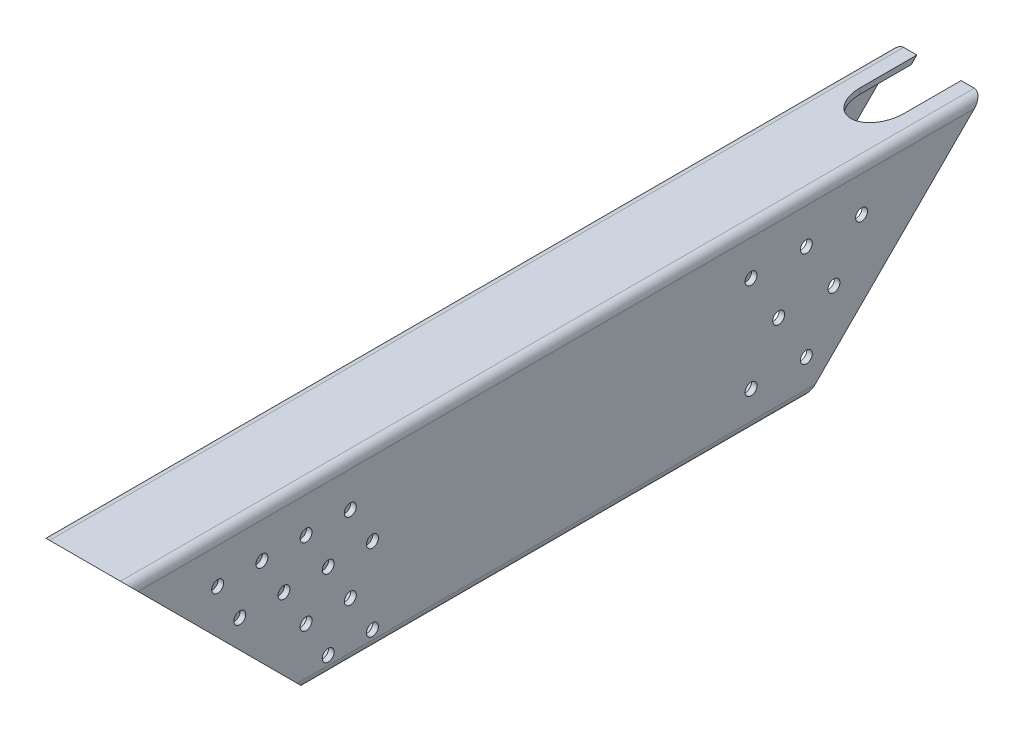
SolidWorks part; units mm, degrees
material "6061-T6 (SS)"
ref_plane "Front" through (0, 0, 0) normal (0, 0, 1) x (1, 0, 0)
ref_plane "Top" through (0, 0, 0) normal (0, 1, 0) x (1, 0, 0)
ref_plane "Right" through (0, 0, 0) normal (1, 0, 0) x (0, 0, -1)
sketch "Sketch3" plane through (0, 0, 0) normal (1, 0, 0) x (0, 0, -1)
  line L0 (-50.8, -25.4) -> (-194.4841, -25.4)
  line L1 (-194.4841, -25.4) -> (-245.2841, 25.4)
  line L2 (-245.2841, 25.4) -> (0, 25.4)
  line L3 (0, 25.4) -> (-50.8, -25.4)
  point P8 (-25.4, 0)
  dimension "D1" = 50.8
  dimension "D2" = 101.6
  dimension "D3" = 45
sketch "Sketch1" plane through (0, 0, 0) normal (0, 0, 1) x (1, 0, 0)
  line L1 (-10.16, -25.4) -> (10.16, -25.4)
  line L2 (-12.7, -22.86) -> (-12.7, 22.86)
  line L3 (-10.16, 25.4) -> (10.16, 25.4)
  line L4 (12.7, -22.86) -> (12.7, 22.86)
  line L5 (-12.7, -25.4) -> (12.7, 25.4) construction
  line L6 (-12.7, 25.4) -> (12.7, -25.4) construction
  arc A0 (-10.16, -25.4) -> (-12.7, -22.86) centre (-10.16, -22.86) cw
  arc A1 (10.16, -25.4) -> (12.7, -22.86) centre (10.16, -22.86) ccw
  arc A2 (10.16, 25.4) -> (12.7, 22.86) centre (10.16, 22.86) cw
  arc A3 (-12.7, 22.86) -> (-10.16, 25.4) centre (-10.16, 22.86) cw
  point P0 (0, 0)
  dimension "D3" = 2.54
  dimension "D1" = 25.4
  dimension "D2" = 50.8
extrude "Extrude-Thin1" add sketch "Sketch1" along normal up to vertex (245.2841 mm away) thin up to point (0, 25.4, 245.2841) thin type one direction reverse wall 1.5875
sketch "Sketch2" plane through (12.7, 0, 0) normal (1, 0, 0) x (0, 0, -1)
  line L0 (-245.2841, 25.4) -> (-194.4841, -25.4)
  line L1 (-245.2841, -25.4) -> (0, -25.4) construction
  line L2 (-194.4841, -25.4) -> (-245.2841, -25.4)
  line L3 (-245.2841, -25.4) -> (-245.2841, 25.4)
  line L4 (0, 25.4) -> (-50.8, -25.4)
  line L5 (-50.8, -25.4) -> (0, -25.4)
  line L6 (0, -25.4) -> (0, 25.4)
  line L7 (0, 25.4) -> (-50.8, -25.4) construction
  line L8 (-194.4841, -25.4) -> (-245.2841, 25.4) construction
extrude "Cut-Extrude1" cut sketch "Sketch2" against normal through all
sketch "Sketch4" plane through (0, 12.7, 12.7) normal (0, -0.7071, -0.7071) x (1, 0, 0)
  circle A0 centre (0, -22.3185) radius 6.35
  circle A1 centre (0, -6.4435) radius 6.35
  circle A2 centre (0, -38.1935) radius 6.35
  dimension "D1" = 12.7
extrude "Cut-Extrude2" cut sketch "Sketch4" against normal through all
sketch "Sketch5" plane through (0, 25.4, 0) normal (0, 1, 0) x (1, 0, 0)
  line L0 (-6.35, -16.2876) -> (-6.35, 0)
  line L1 (-6.35, 0) -> (6.35, 0)
  line L2 (6.35, 0) -> (6.35, -16.2876)
  line L3 (-4.6185, 0) -> (-10.16, 0) construction
  ellipse E1 centre (0, -16.2876) end of major axis (0, -7.3073) minor radius 6.35 construction
  ellipse E3 centre (0, -16.2876) end of major axis (0, -7.3073) minor radius 6.35 (-6.35, -16.2876) -> (6.35, -16.2876) ccw
extrude "Cut-Extrude3" cut sketch "Sketch5" against normal through all
hole_wizard "1/8 (0.135) Diameter Hole1" positions "Sketch6" profile "Sketch7" hole size "1/8" standard "ANSI Inch" end condition through all
sketch "Sketch6" plane through (-12.7, 0, 0) normal (-1, 0, 0) x (0, 0, 1)
  point P0 (34.925, 12.7)
  point P3 (50.8, 12.7)
  point P6 (42.8625, -1.0482)
  point P9 (58.7375, -1.0482)
  point P12 (66.675, -14.7963)
  point P15 (50.8, -14.7963)
  point P18 (66.675, 12.7)
  point P21 (219.8841, 12.7)
  point P24 (213.5341, 1.7015)
  point P27 (207.1841, 12.7)
  point P30 (194.4841, 12.7)
  point P33 (181.7841, 12.7)
  point P36 (175.4341, 1.7015)
  point P39 (188.1341, 1.7015)
  point P42 (200.8341, 1.7015)
  point P45 (194.4841, -9.297)
  point P48 (181.7841, -9.297)
  point P51 (175.4341, -20.2956)
  point P54 (188.1341, -20.2956)
sketch "Sketch7" plane through (-12.7, 12.7, 34.925) normal (0, 1, 0) x (0, 0, 1)
  line L0 (0, 0) -> (0, 25.4)
  line L1 (0, 25.4) -> (1.7145, 25.4)
  line L2 (1.7145, 25.4) -> (1.7145, 0)
  line L5 (1.7145, 0) -> (0, 0)
  line L11 (0, -6.35) -> (0, 107.95) construction
  dimension "Thru Hole Dia." = 3.429
  dimension "Thru Hole Depth" = 25.4
